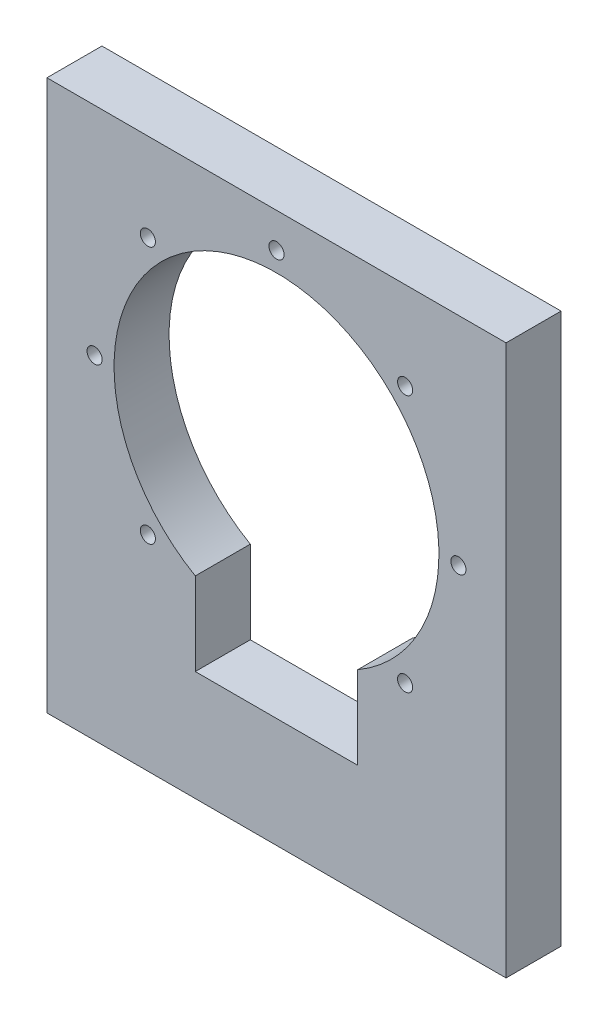
SolidWorks part; units mm, degrees
material "1060 Alloy"
ref_plane "Front Plane" through (0, 0, 0) normal (0, 0, 1) x (1, 0, 0)
ref_plane "Top Plane" through (0, 0, 0) normal (0, 1, 0) x (1, 0, 0)
ref_plane "Right Plane" through (0, 0, 0) normal (1, 0, 0) x (0, 0, -1)
sketch "Sketch1" plane through (0, 0, 0) normal (0, 0, 1) x (1, 0, 0)
  line L1 (0, 76.2) -> (106, 76.2)
  line L5 (0, 76.2) -> (0, -50.8)
  line L6 (0, -50.8) -> (106, -50.8)
  line L7 (0, 76.2) -> (0, -50.8) construction
  line L8 (53, 26.2) -> (53, -11.3) construction
  line L9 (53, 26.2) -> (34.25, -6.276) construction
  line L10 (53, 26.2) -> (71.75, -6.276) construction
  line L11 (34.25, -6.276) -> (34.25, -25.4)
  line L12 (71.75, -6.276) -> (71.75, -25.4)
  line L13 (71.75, -25.4) -> (34.25, -25.4)
  line L21 (106, 76.2) -> (106, -50.8)
  arc A6 (71.75, -6.276) -> (34.25, -6.276) centre (53, 26.2) ccw
  circle A7 centre (53, 26.2) radius 42 construction
  circle A9 centre (82.6985, 55.8985) radius 1.746
  circle A10 centre (95, 26.2) radius 1.746
  circle A11 centre (82.6985, -3.4985) radius 1.746
  circle A13 centre (23.3015, -3.4985) radius 1.746
  circle A14 centre (11, 26.2) radius 1.746
  circle A15 centre (23.3015, 55.8985) radius 1.746
  circle A33 centre (53, 68.2) radius 1.746
  point P0 (0, 0)
  point P6 (53, 26.2)
  point P32 (53, 26.2)
  point P38 (53, 26.2)
  dimension "D6" = 75
  dimension "D7" = 84
  dimension "D8" = 3.492
  dimension "D9" = 3.492
  dimension "D4" = 53
  dimension "D5" = 50
  dimension "D10" = 30
  dimension "D11" = 30
  dimension "D2" = 25.4
  dimension "D12" = 127
  dimension "D13" = 106
extrude "Boss-Extrude1" add sketch "Sketch1" along normal blind 12.7
equation "\"bplate_length\"= 24in"
equation "\"bplate_height\"= 6in"
equation "\"bplate_thickness\"= 0.5in"
equation "\"motor_diameter\"= 96 / 25.4in"
equation "\"motor_clearance\"= 5 / 25.4in"
equation "\"motor_mount_hole_pattern_dia\"= 84 / 25.4in"
equation "\"motor_mount_hole_dia\"= 4 / 25.4in"
equation "\"motor_cx\"= \"motor_clearance\" + \"motor_diameter\" / 2in"
equation "\"motor_cy_top\"= \"motor_mount_hole_pattern_dia\" / 2 + \"motor_mount_hole_dia\" * 2in"
equation "\"motor_driver_cover_dia\"= 75 / 25.4in"
equation "\"D4@Sketch1\"=\"motor_cx\""
equation "\"motor_driver_cutout_clearance\"= 60deg"
equation "\"wire_cutout_clearance\"= 2in"
equation "\"connector_plate_thickness\"= 1in"
equation "\"connector_plate_hole_diameter\"= 0.5in"
equation "\"connector_plate_hole_depth\"= 1in"
equation "\"coonector_first_hole_offset\"= 1.6in"
equation "\"D6@Sketch1\"=\"motor_driver_cover_dia\""
equation "\"D7@Sketch1\"=\"motor_mount_hole_pattern_dia\""
equation "\"D8@Sketch1\"=\"motor_mount_hole_dia\"  - 0.02"
